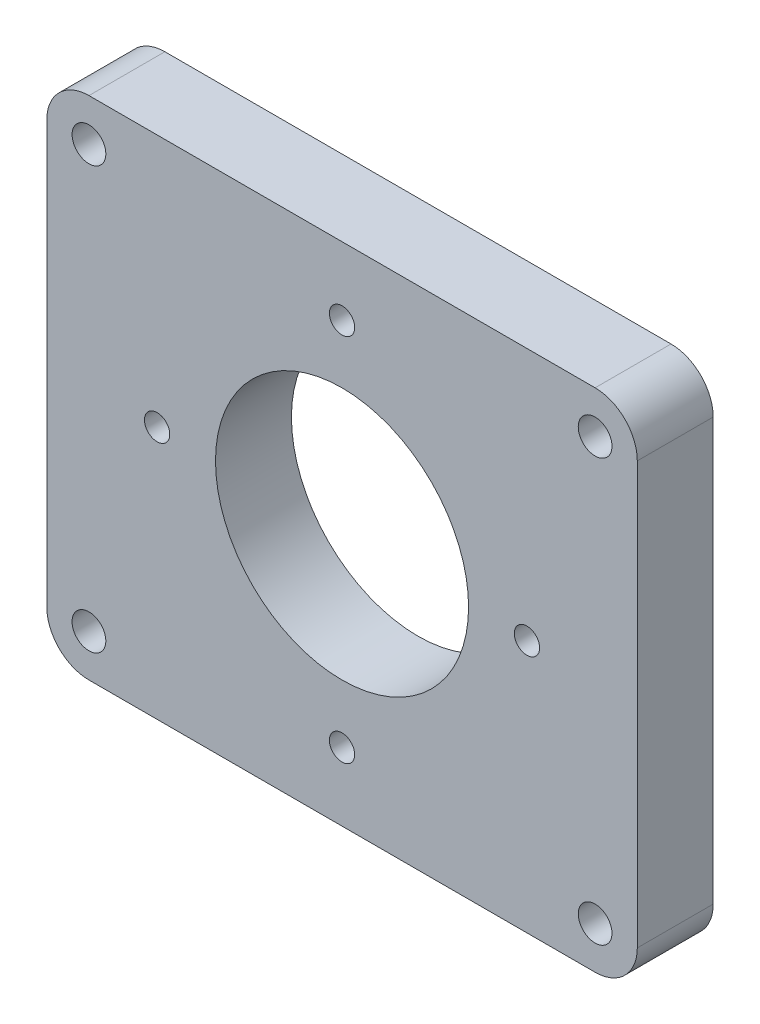
SolidWorks part; units mm, degrees
ref_plane "Front" through (0, 0, 0) normal (0, 0, 1) x (1, 0, 0)
ref_plane "Top" through (0, 0, 0) normal (0, 1, 0) x (1, 0, 0)
ref_plane "Right" through (0, 0, 0) normal (1, 0, 0) x (0, 0, -1)
sketch "Esquisse1" plane through (0, 0, 0) normal (0, 0, 1) x (1, 0, 0)
  line L1 (0, 0) -> (70, 0)
  line L2 (0, 0) -> (0, 60)
  line L3 (0, 60) -> (70, 60)
  line L4 (70, 0) -> (70, 60)
  dimension "D1" = 70
  dimension "D2" = 60
extrude "Boss.-Extru.1" add sketch "Esquisse1" along normal blind 9
sketch "Esquisse2" plane through (0, 0, 9) normal (0, 0, 1) x (1, 0, 0)
  line L0 (35, 60) -> (35, 0) construction
  line L1 (70, 60) -> (0, 60) construction
  line L2 (0, 0) -> (70, 0) construction
  line L3 (0, 60) -> (0, 0) construction
  line L4 (35, 30) -> (56.9203, 30) construction
  line L5 (56.9203, 30) -> (35, 51.9203) construction
  line L6 (35, 30) -> (32.7843, 32.2157) construction
  line L7 (35, 8.0797) -> (13.0797, 30) construction
  line L8 (35, 30) -> (35, 8.0797) construction
  circle A0 centre (35, 30) radius 15
  circle A1 centre (56.9203, 30) radius 1.5
  circle A2 centre (35, 51.9203) radius 1.5
  circle A3 centre (13.0797, 30) radius 1.5
  circle A4 centre (35, 8.0797) radius 1.5
  circle A5 centre (5, 55) radius 2
  circle A6 centre (65, 55) radius 2
  circle A7 centre (65, 5) radius 2
  circle A8 centre (5, 5) radius 2
  dimension "D2" = 30
  dimension "D4" = 3
  dimension "D9" = 4
  dimension "D1" = 35
  dimension "D3" = 90
  dimension "D5" = 45
  dimension "D6" = 31
  dimension "D7" = 60
  dimension "D8" = 50
extrude "Enlèv. mat.-Extru.1" cut sketch "Esquisse2" against normal through all
fillet "Congé1" radius 5 4 edges at (70, 0, 4.5) (0, 0, 4.5) (70, 60, 4.5) (0, 60, 4.5)
